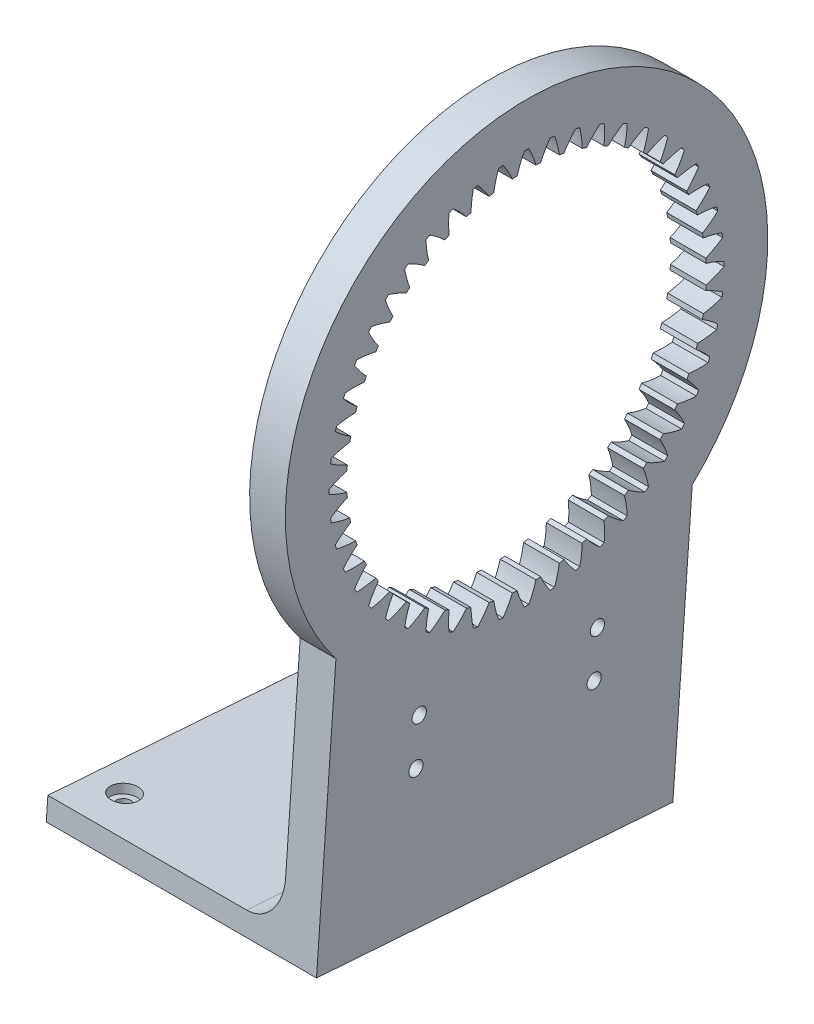
SolidWorks part; units mm, degrees
material "PLA personnalisé"
ref_plane "Plane1" through (0, 0, 0) normal (0, 0, 1) x (1, 0, 0)
ref_plane "Plane2" through (0, 0, 0) normal (0, 1, 0) x (1, 0, 0)
ref_plane "Plane3" through (0, 0, 0) normal (1, 0, 0) x (0, 0, -1)
other "Configuration Table"
sketch "HoldingSke" plane through (0, 0, 0) normal (0, 1, 0) x (1, 0, 0)
  line L0 (0, 0) -> (0.3824, -0.4247)
  line L1 (-15, 0) -> (100, 0) construction
  line L2 (0, 0) -> (-2.1039, 2.3779)
  line L3 (0, 0) -> (-11.863, 4.5341)
  line L4 (0, 0) -> (5.7786, 6.4178)
  line L5 (0, 0) -> (-23.7986, -8.8762)
  line L6 (0, 0) -> (-10.5278, -7.1032)
  line L7 (-2.1039, 2.3779) -> (3.3635, 27.1825)
  line L8 (-76.2, 4.1279) -> (-54.61, 4.1279)
  line L9 (-71.009, 38.7566) -> (-53.1078, 45.2721)
  line L10 (-76.2, 71.12) -> (104.1128, 71.12)
  line L11 (0, 0) -> (-8, 0)
  line L12 (-76.2, 101.6) -> (-76.147, 101.6)
  line L13 (24.9733, 27.94) -> (52.9518, 28.4284)
  line L14 (24.9733, 27.94) -> (24.9743, 27.94)
  line L15 (24.9733, 27.94) -> (100.4006, 29.5858)
  circle A0 centre (0, 0) radius 54
  circle A1 centre (0, 0) radius 12.7
  circle A2 centre (0, 0) radius 12.7
  dimension "Num_teeth" = 48
  dimension "Pitch_radius" = 180.3128
  dimension "Width" = 8
  dimension "Diameter" = 108
sketch "BasProSke" plane through (0, 0, 0) normal (0, 1, 0) x (1, 0, 0)
  line L0 (-10, 0) -> (60, 0) construction
  line L1 (0, 40.25) -> (0, 54)
  line L2 (0, 40.25) -> (8, 40.25)
  line L3 (8, 40.25) -> (8, 54)
  line L4 (8, 54) -> (0, 54)
  dimension "Thickness" = 8
  dimension "Diameter" = 108
revolve "Base-Revolve" add sketch "BasProSke" angle 360 about L0
sketch "TooCutSke" plane through (0, 0, 0) normal (1, 0, 0) x (0, 0, -1)
  line L3 (1.5067, 41.973) -> (1.5067, 53.6633) construction
  line L4 (0, 0) -> (0, 59.563) construction
  line L5 (0, 0) -> (-4.4688, 68.1812) construction
  line L6 (-18.0846, 34.4113) -> (35.4386, 37.9194) construction
  circle A0 centre (0, 0) radius 42 construction
  circle A1 centre (0, 0) radius 44.1885 construction
  circle A2 centre (0, 0) radius 35.5204 construction
  circle A3 centre (0, 0) radius 40.2246 construction
  arc A4 (2.1106, 40.1692) -> (0.502, 44.1856) centre (-18.0846, 34.4113) ccw
  arc A5 (2.1106, 40.1692) -> (-2.1106, 40.1692) centre (0, 0) ccw
  arc A6 (0.502, 44.1856) -> (-0.502, 44.1856) centre (0, 0) ccw
  arc A7 (-0.502, 44.1856) -> (-2.1106, 40.1692) centre (18.0846, 34.4113) ccw
extrude "ToothCut" cut sketch "TooCutSke" along normal through all
fillet "Breaks" [suppressed] radius 0.175
fillet "RootFillets" [suppressed] radius 0.4385
pattern_circular "TeethCuts" count 48 over 360 about axis through (-10, 0, 0) along (1, 0, 0) of "RootFillets", "Breaks", "ToothCut"
sketch "Esquisse1" plane through (8, 0, 0) normal (1, 0, 0) x (0, 0, -1)
  circle A0 centre (0, 0) radius 44.1885
  circle A1 centre (0, 0) radius 48.6885
  circle A2 centre (3.5329, 48.5602) radius 1.6
  dimension "D1" = 4.5
  dimension "D2" = 3.2
extrude "Enlèv. mat.-Extru.1" cut sketch "Esquisse1" against normal blind 10 contours A2
pattern_circular "Répétition circulaire1" count 6 over 360 about axis through (8, 0, 0) along (-1, 0, 0) of "Enlèv. mat.-Extru.1"
sketch "Esquisse2" plane through (8, 0, 0) normal (1, 0, 0) x (0, 0, -1)
  line L0 (-41.8261, -21.3656) -> (37.963, -27.1706) construction
  line L1 (-41.8261, -21.3656) -> (37.963, -27.1706)
  line L2 (-41.8261, -21.3656) -> (-47.0256, -92.8324)
  line L3 (37.963, -27.1706) -> (32.7635, -98.6374)
  line L4 (-47.0256, -92.8324) -> (32.7635, -98.6374)
  line L5 (0, 0) -> (-7.131, -95.7349) construction
  line L6 (-44.4258, -57.099) -> (-4.4748, -60.0748) construction
  line L7 (35.3633, -62.904) -> (-4.4748, -60.0748) construction
  circle A0 centre (0, 0) radius 54
  dimension "D1" = 96
  dimension "D2" = 80
extrude "Boss.-Extru.1" add sketch "Esquisse2" against normal through all contours A0 L2 L4 L3 region at (8, -71.7912, 5.4319)
sketch "Esquisse3" plane through (8, 0, 0) normal (1, 0, 0) x (0, 0, -1)
  circle A0 centre (-3.5329, -48.5602) radius 2.4787
extrude "Boss.-Extru.2" add sketch "Esquisse3" against normal blind 8
pattern_circular "Répétition circulaire3" count 6 over 360 about axis through (8, 0, 0) along (-1, 0, 0) of "Boss.-Extru.2"
sketch "Esquisse4" plane through (0, 0, 0) normal (-1, 0, 0) x (0, 0, 1)
  line L0 (7.131, -95.7349) -> (0, 0) construction
  line L1 (47.0256, -92.8324) -> (-32.7635, -98.6374) construction
  line L2 (44.0455, -51.8715) -> (-35.7336, -57.8141) construction
  line L3 (42.6786, -33.0838) -> (47.0256, -92.8324) construction
  line L4 (-37.084, -39.2527) -> (-32.7635, -98.6374) construction
  line L5 (-35.008, -67.7877) -> (44.7711, -61.8452) construction
  circle A0 centre (-15.8593, -56.3337) radius 1.6
  circle A1 centre (-15.1165, -66.3061) radius 1.6
  circle A2 centre (24.773, -63.3348) radius 1.6
  circle A3 centre (24.0302, -53.3624) radius 1.6
  dimension "D3" = 3.2
  dimension "D4" = 3.2
  dimension "D1" = 55
  dimension "D2" = 10
  dimension "D5" = 20
  dimension "D6" = 20
extrude "Enlèv. mat.-Extru.2" cut sketch "Esquisse4" against normal blind 10
sketch "Esquisse5" plane through (8, 0, 0) normal (1, 0, 0) x (0, 0, -1)
  line L0 (-47.0256, -92.8324) -> (32.7635, -98.6374)
  line L1 (32.7635, -98.6374) -> (33.1264, -93.6506)
  line L2 (37.084, -39.2527) -> (32.7635, -98.6374) construction
  line L3 (33.1264, -93.6506) -> (-46.6628, -87.8456)
  line L4 (-42.6786, -33.0838) -> (-47.0256, -92.8324) construction
  line L5 (-46.6628, -87.8456) -> (-47.0256, -92.8324)
  dimension "D1" = 5
extrude "Boss.-Extru.3" add sketch "Esquisse5" against normal blind 52.5 from offset 8 offset against normal yes
fillet "Congé1" radius 8 1 edges at (0, -90.7481, 6.7682) second distance 10 first distance on face at (-26.25, -90.7481, 6.7682)
sketch "Esquisse6" plane through (0, -90.7601, 6.6032) normal (0, 0.9974, -0.0726) x (1, 0, 0)
  line L0 (-52.5, -0.1655) -> (-140.1065, -0.1655) construction
  line L1 (-52.5, 39.8345) -> (-52.5, -40.1655) construction
  line L2 (-52.5, -0.1655) -> (-8, -0.1655) construction
  line L3 (-8, -40.1655) -> (-8, 39.8345) construction
  circle A0 centre (-62.5, -0.1655) radius 35
  circle A1 centre (-27.5, -0.1655) radius 3
  point P23 (-62, 3.2986)
  point P24 (-62, -0.1655)
  dimension "D2" = 70
  dimension "D3" = 6
  dimension "D1" = 10
extrude "Enlèv. mat.-Extru.3" cut sketch "Esquisse6" against normal blind 2 contours A1
sketch "Esquisse7" plane through (0, -90.7601, 6.6032) normal (0, 0.9974, -0.0726) x (1, 0, 0)
  circle A0 centre (-27.5, -0.1655) radius 1.6
  dimension "D3" = 3.2
extrude "Enlèv. mat.-Extru.4" cut sketch "Esquisse7" against normal blind 5
ref_axis "Axe1" through (-62.5, -90.7481, 6.7682) along (0, 0.9974, -0.0726)
pattern_circular "Répétition circulaire4" count 6 over 360 about axis through (-62.5, -90.7481, 6.7682) along (0, 0.9974, -0.0726) of "Enlèv. mat.-Extru.3", "Enlèv. mat.-Extru.4"
equation "' \"Module@HoldingSke\" = 6.35"
equation "' \"Num_teeth@HoldingSke\" = 24"
equation "' \"Ap@HoldingSke\" =  14.5"
equation "' \"Ap@HoldingSke\" = 14.5"
equation "' \"Width@HoldingSke\" = 12"
equation "' \"Diameter@HoldingSke\" = 8 * 25.4"
equation "' \"Show_teeth@HoldingSke\" = 100"
equation "' \"Backlash@HoldingSke\" = 0.009 * 25.4"
equation "' \"Addendum_fac@HoldingSke\" = 1.0"
equation "' \"Dedendum_fac@HoldingSke\" = 1.25"
equation "' \"Dedendum_add@HoldingSke\" = 0.00005 * 25.4"
equation "' \"Clearance_fac@HoldingSke\" = 0.25"
equation "\"Pitch@HoldingSke\" = 1 / \"Module@HoldingSke\" "
equation "\"Overcut_dia@TooCutSke\" = (\"Num_teeth@HoldingSke\" - 2 * \"Addendum_fac@HoldingSke\") / \"Pitch@HoldingSke\" - 0.002 * 25.4"
equation "\"Pitch_dia@TooCutSke\" = \"Num_teeth@HoldingSke\" / \"Pitch@HoldingSke\""
equation "\"Base_dia@TooCutSke\" = \"Num_teeth@HoldingSke\" / \"Pitch@HoldingSke\" * cos((\"Ap@HoldingSke\"  * 3.14159265 / 180)) * 0.90"
equation "\"Root_dia@TooCutSke\" = \"Num_teeth@HoldingSke\"  / \"Pitch@HoldingSke\" + 2 *  \"Dedendum_fac@HoldingSke\"/ \"Pitch@HoldingSke\" + \"Dedendum_add@HoldingSke\" * 2"
equation "\"Half_ang@TooCutSke\" = 180 / \"Num_teeth@HoldingSke\""
equation "\"Half_CT@TooCutSke\" = \"Num_teeth@HoldingSke\" / \"Pitch@HoldingSke\" * sin((3.14159265 / 2 / \"Num_teeth@HoldingSke\")) / 2 + 10 * \"Backlash@HoldingSke\" / 4"
equation "\"Flank_rad@TooCutSke\" = \"Num_teeth@HoldingSke\" / \"Pitch@HoldingSke\" / 4"
equation "\"Radius@RootFillets\"= \"Clearance_fac@HoldingSke\" / \"Pitch@HoldingSke\" + \"Dedendum_add@HoldingSke\""
equation "\"Break_rad@Breaks\" = 0.02 / \"Pitch@HoldingSke\" * 5"
equation "\"Num_teeth@TeethCuts\" = int( \"Show_teeth@HoldingSke\" ) + 1"
equation "\"Num_teeth@TeethCuts\" = ((sgn( \"Num_teeth@TeethCuts\" - \"Num_teeth@HoldingSke\" )-1)*( \"Num_teeth@TeethCuts\" - \"Num_teeth@HoldingSke\" ))/-2+ \"Num_teeth@HoldingSke\""
equation "\"Num_teeth@TeethCuts\" = ((sgn( \"Num_teeth@TeethCuts\" - 2.0)+1)*( \"Num_teeth@TeethCuts\" - 2.0))/2 +2.0"
equation "\"Angle@TeethCuts\" = 360.0 / \"Num_teeth@HoldingSke\""
equation "\"Diameter@BasProSke\" = \"Num_teeth@HoldingSke\"  / \"Pitch@HoldingSke\" + 2 *  \"Dedendum_fac@HoldingSke\"/ \"Pitch@HoldingSke\" + \"Dedendum_add@HoldingSke\" * 2 + 0.002 * 25.4"
equation "\"Diameter@BasProSke\" = ((sgn( \"Diameter@BasProSke\"  - \"Diameter@HoldingSke\" )+1)*( \"Diameter@BasProSke\"  - \"Diameter@HoldingSke\" ))/2 + \"Diameter@HoldingSke\""
equation "\"Inside_diameter@BasProSke\" =  (\"Num_teeth@HoldingSke\" - 2 * \"Addendum_fac@HoldingSke\") / \"Pitch@HoldingSke\" "
equation "\"Thickness@BasProSke\"  = \"Width@HoldingSke\""
